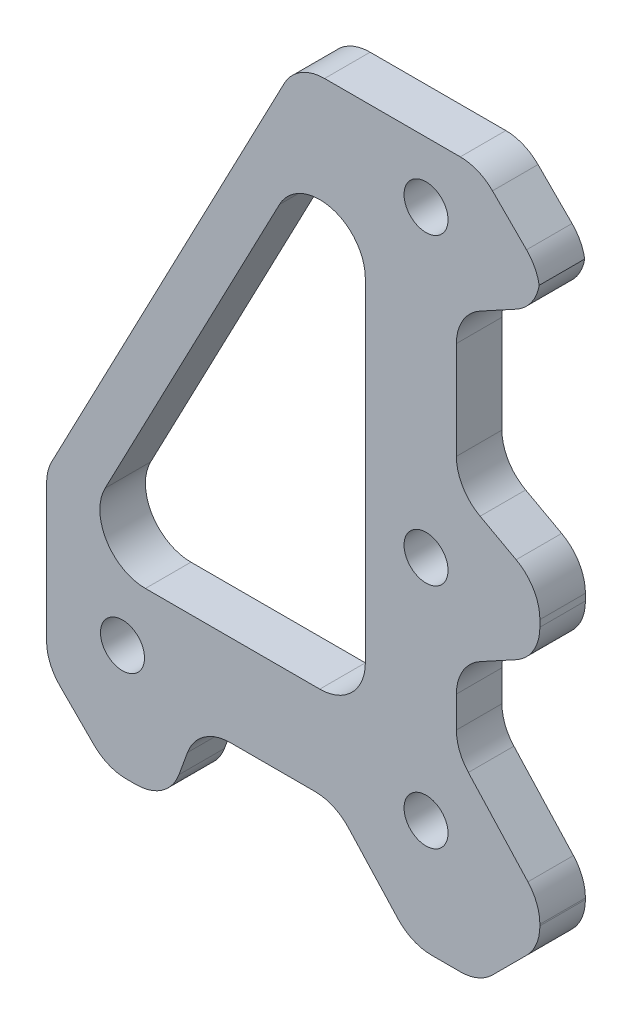
SolidWorks part; units mm, degrees
material "Thornel Mat VMA"
ref_plane "前视基准面" through (0, 0, 0) normal (0, 0, 1) x (1, 0, 0)
ref_plane "上视基准面" through (0, 0, 0) normal (0, 1, 0) x (1, 0, 0)
ref_plane "右视基准面" through (0, 0, 0) normal (1, 0, 0) x (0, 0, -1)
sketch "草图1" plane through (0, 0, 0) normal (0, 0, 1) x (1, 0, 0)
  line L0 (-20, 0) -> (0, 0) construction
  line L1 (0, 0) -> (0, 35) construction
  line L2 (-25, 7.5) -> (-25, -7.5)
  line L3 (-25, -7.5) -> (7.5, -7.5)
  line L4 (7.5, -7.5) -> (7.5, 39)
  line L5 (7.5, 39) -> (-8.5, 39)
  line L6 (-8.5, 39) -> (-25, 7.5)
  line L7 (-9.6575, 30.3248) -> (-21.1461, 8.392)
  line L8 (-18.4886, 4) -> (-4, 4)
  line L9 (-4, 4) -> (-4, 28.9328)
  circle A0 centre (-20, 0) radius 1.45
  circle A1 centre (0, 0) radius 1.45
  circle A2 centre (0, 15) radius 1.45
  circle A3 centre (0, 35) radius 1.45
  arc A4 (-21.1461, 8.392) -> (-18.4886, 4) centre (-18.4886, 7) ccw
  arc A5 (-9.6575, 30.3248) -> (-4, 28.9328) centre (-7, 28.9328) cw
  point P16 (-25, 0)
  dimension "D1" = 2.9
  dimension "D7" = 4
  dimension "D14" = 3
  dimension "D2" = 20
  dimension "D3" = 15
  dimension "D4" = 20
  dimension "D5" = 7.5
  dimension "D6" = 7.5
  dimension "D8" = 16
  dimension "D9" = 5
  dimension "D10" = 15
  dimension "D11" = 4
  dimension "D12" = 4
  dimension "D13" = 3
extrude "凸台-拉伸1" add sketch "草图1" along normal blind 3
chamfer "倒角1" distance 4 angle 45 3 edges at (-25, -7.5, 1.5) (7.5, -7.5, 1.5) (7.5, 39, 1.5)
sketch "草图2" plane through (0, 0, 3) normal (0, 0, 1) x (1, 0, 0)
  line L0 (-17, -7.5) -> (-15, -2)
  line L1 (-21, -7.5) -> (3.5, -7.5) construction
  line L2 (-15, -2) -> (-6, -2)
  line L3 (-6, -2) -> (-0.9583, -7.5)
  line L4 (-0.9583, -7.5) -> (-17, -7.5)
  line L5 (7.5, 33) -> (2, 30)
  line L6 (7.5, -3.5) -> (7.5, 35) construction
  line L7 (2, 30) -> (2, 20)
  line L8 (2, 20) -> (7.5, 17)
  line L9 (7.5, 17) -> (7.5, 33)
  line L10 (7.5, 13) -> (2, 10)
  line L11 (2, 10) -> (2, 5)
  line L12 (2, 5) -> (7.5, -1)
  line L13 (7.5, -1) -> (7.5, 13)
  line L15 (-4, 4) -> (-4, 28.9328) construction
  line L16 (-18.4886, 4) -> (-4, 4) construction
  circle A0 centre (0, 15) radius 1.45 construction
  circle A1 centre (0, 35) radius 1.45 construction
  circle A2 centre (0, 0) radius 1.45 construction
  circle A3 centre (-20, 0) radius 1.45 construction
  dimension "D1" = 2
  dimension "D5" = 2
  dimension "D6" = 5
  dimension "D7" = 1
  dimension "D12" = 6
  dimension "D13" = 3
  dimension "D2" = 5
  dimension "D3" = 2
  dimension "D4" = 5
  dimension "D8" = 5
  dimension "D9" = 6
  dimension "D10" = 6
  dimension "D11" = 6
  dimension "D14" = 5
extrude "切除-拉伸1" cut sketch "草图2" against normal through all
fillet "圆角1" radius 3 1 edges at (-4, 4, 1.5)
fillet "圆角2" radius 3 20 edges at (-6, -2, 1.5) (-0.9583, -7.5, 1.5) (3.5, -7.5, 1.5) (7.5, -3.5, 1.5) (7.5, -1, 1.5) (2, 5, 1.5) (2, 10, 1.5) (7.5, 13, 1.5) (7.5, 17, 1.5) (2, 20, 1.5) (2, 30, 1.5) (7.5, 33, 1.5) (7.5, 35, 1.5) (3.5, 39, 1.5) (-8.5, 39, 1.5) (-25, 7.5, 1.5) (-21, -7.5, 1.5) (-17, -7.5, 1.5) (-15, -2, 1.5) (-25, -3.5, 1.5)
